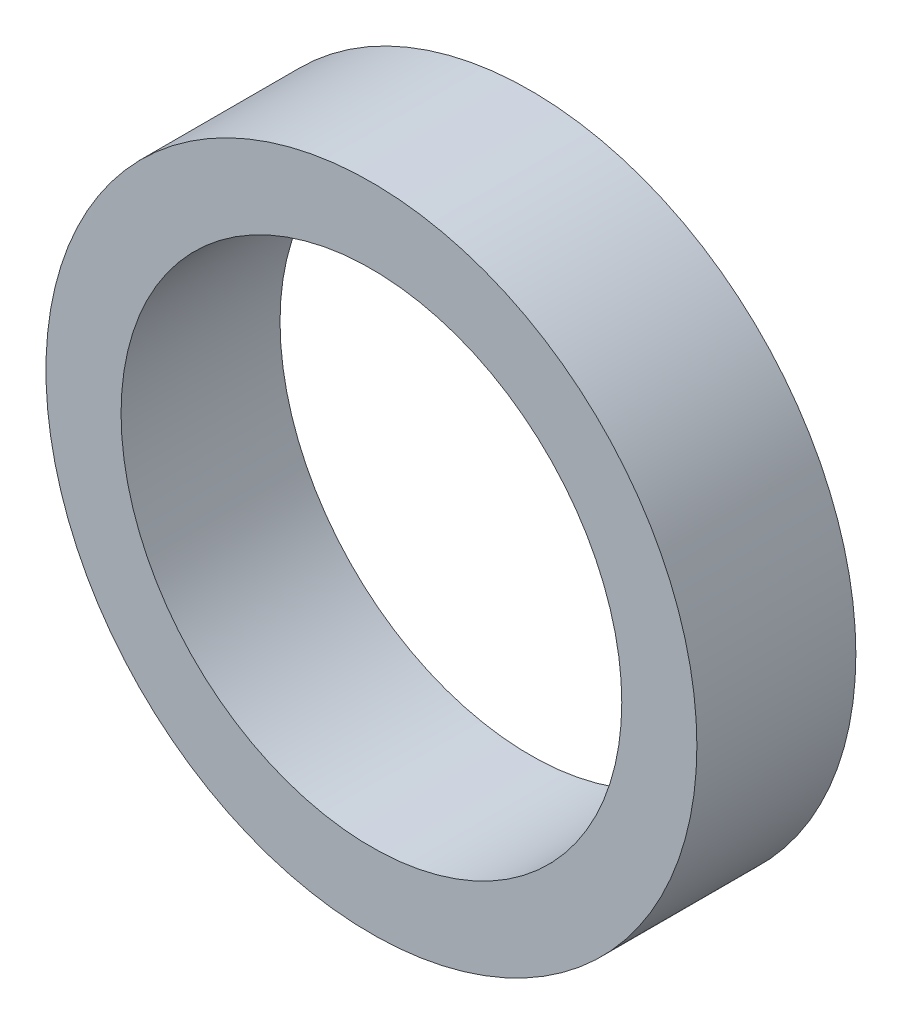
SolidWorks part; units mm, degrees
material "6061 Alloy"
ref_plane "Front Plane" through (0, 0, 0) normal (0, 0, 1) x (1, 0, 0)
ref_plane "Top Plane" through (0, 0, 0) normal (0, 1, 0) x (1, 0, 0)
ref_plane "Right Plane" through (0, 0, 0) normal (1, 0, 0) x (0, 0, -1)
sketch "Sketch1" plane through (0, 0, 0) normal (0, 0, 1) x (1, 0, 0)
  circle A0 centre (0, 0) radius 6.5
  circle A1 centre (0, 0) radius 5
  dimension "D1" = 13
  dimension "ID" = 10
extrude "Extrude1" add sketch "Sketch1" along normal mid plane 3.175
sketch "Sketch2" plane through (0, 0, 0) normal (1, 0, 0) x (0, 0, -1)
  line L0 (-1.5875, -5) -> (1.5875, -5) construction
  line L3 (1.5875, 5) -> (-1.5875, 5) construction
  line L5 (-1.5875, -5) -> (1.5875, -5)
  line L6 (1.5875, 5) -> (-1.5875, 5)
sketch "Sketch4" plane through (0, 0, 1.5875) normal (0, 0, 1) x (1, 0, 0)
  line L0 (0, 0) -> (-3.5355, 3.5355)
  line L1 (0, -1.7463) -> (0, 1.7463) construction
  circle A0 centre (0, 0) radius 5 construction
  dimension "D1" = 45
ref_axis "Center Axis 1" through (0, 0, 1.5875) along (0, 0, -1)
ref_plane "Contact Plane 1" through (0, 0, 1.5875) normal (0, 0, 1) x (1, 0, 0)
ref_plane "Contact Plane 2" through (0, 0, -1.5875) normal (0, 0, -1) x (-1, 0, 0)
